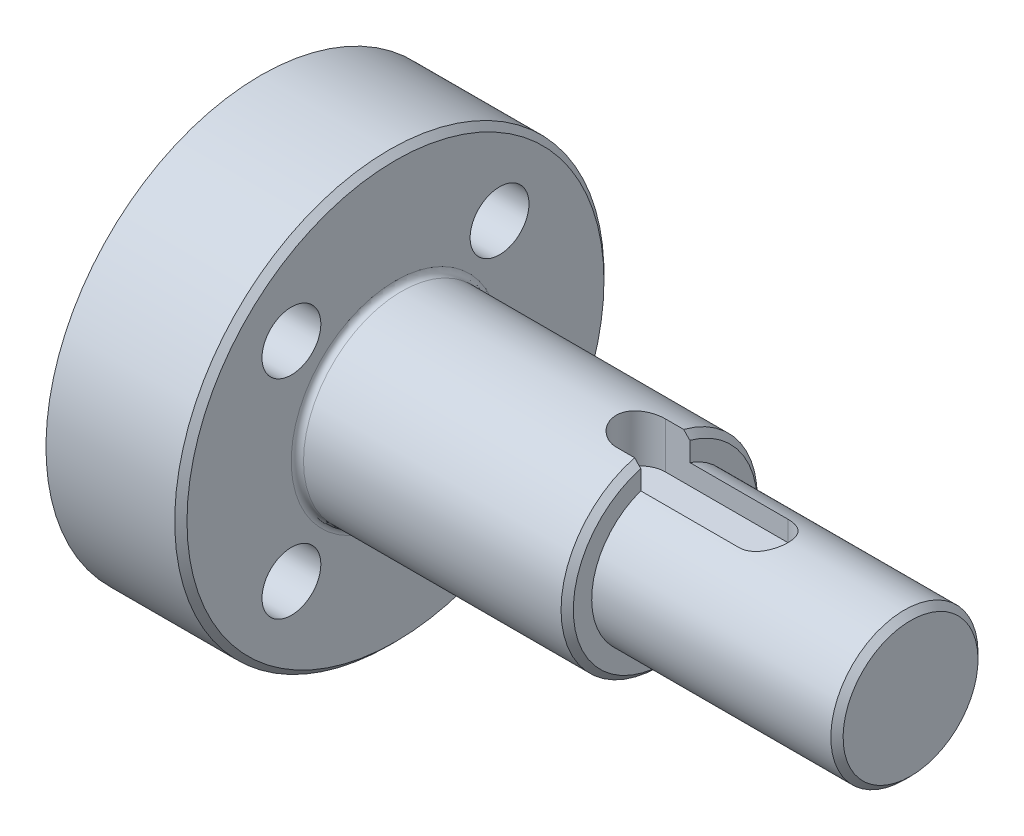
SolidWorks part; units mm, degrees
material "6061-T6 "
ref_plane "Front Plane" through (0, 0, 0) normal (0, 0, 1) x (1, 0, 0)
ref_plane "Top Plane" through (0, 0, 0) normal (0, 1, 0) x (1, 0, 0)
ref_plane "Right Plane" through (0, 0, 0) normal (1, 0, 0) x (0, 0, -1)
sketch "Sketch1" plane through (0, 0, 0) normal (0, 0, 1) x (1, 0, 0)
  line L0 (0, 0) -> (0, 8)
  line L1 (-0.75, 8) -> (-2.5, 8)
  line L2 (-2.5, 8) -> (-2.5, 8.75)
  line L3 (-2.5, 8.75) -> (3, 8.75)
  line L4 (3, 8.75) -> (3, 4)
  line L5 (3, 4) -> (14, 4)
  line L6 (14, 4) -> (14, 3)
  line L7 (14, 3) -> (24, 3)
  line L8 (24, 3) -> (24, 0)
  line L9 (24, 0) -> (0, 0)
  line L11 (6, 4) -> (6, 6) construction
  line L12 (6, 6) -> (9.5, 6) construction
  line L13 (9.5, 6) -> (9.5, 4) construction
  line L14 (14, 4) -> (14, 6.8) construction
  line L15 (14, 6.8) -> (18, 6.8) construction
  line L16 (18, 6.8) -> (18, 3) construction
  line L17 (9.5, 6) -> (11.5, 6) construction
  line L18 (11.5, 6) -> (11.5, 8) construction
  line L19 (0, 0) -> (-3, 0) construction
  line L20 (-3, 0) -> (-3, 8) construction
  line L21 (-3, 8) -> (-2.7343, 8) construction
  line L22 (19, 3) -> (19, 5) construction
  line L23 (19, 5) -> (22, 5) construction
  line L24 (22, 5) -> (22, 3) construction
  line L25 (-0.375, 8.2165) -> (-0.75, 8)
  arc A0 (0, 8) -> (-0.375, 8.2165) centre (-0.25, 8) ccw
  dimension "D22" = 0.5
  dimension "D1" = 8
  dimension "D2" = 2.5
  dimension "D3" = 0.75
  dimension "D4" = 3
  dimension "D5" = 4
  dimension "D7" = 3
  dimension "D8" = 3.5
  dimension "D9" = 6
  dimension "D10" = 3
  dimension "D11" = 2
  dimension "D12" = 4
  dimension "D13" = 6.8
  dimension "D14" = 2.5
  dimension "D15" = 3
  dimension "D16" = 3
  dimension "D17" = 1
  dimension "D18" = 5
  dimension "D19" = 2
  dimension "D21" = 30
revolve "Revolve1" add sketch "Sketch1" angle 360 about L9 region at (9.6178, 2.5742, 0)
hole_wizard "M2 Clearance Hole2" positions "Sketch3" profile "Sketch4" hole size "M2" standard "ANSI Metric" end condition through all
sketch "Sketch3" plane through (3, 0, 0) normal (1, 0, 0) x (0, 0, -1)
  line L0 (-4.2426, 4.2426) -> (4.2426, -4.2426) construction
  line L2 (4.2426, 4.2426) -> (-4.2426, -4.2426) construction
  line L4 (0, 0) -> (0, 6) construction
  circle A0 centre (0, 0) radius 6 construction
  circle A1 centre (-4.2426, 4.2426) radius 1.75 construction
  point P6 (-4.2426, 4.2426)
  point P7 (4.2426, -4.2426)
  point P9 (4.2426, 4.2426)
  point P10 (-4.2426, -4.2426)
  point P25 (-4.2426, 4.2426)
  point P27 (-4.2426, -4.2426)
  point P29 (4.2426, -4.2426)
  point P31 (4.2426, 4.2426)
  dimension "D1" = 12
  dimension "D3" = 3.5
  dimension "D2" = 45
sketch "Sketch4" plane through (3, 4.2426, -4.2426) normal (0, 1, 0) x (0, 0, -1)
  line L0 (0, 0) -> (0, 5.5)
  line L1 (0, 5.5) -> (1.2, 5.5)
  line L2 (1.2, 5.5) -> (1.2, 0)
  line L5 (1.2, 0) -> (0, 0)
  line L11 (0, -6.35) -> (0, 107.95) construction
  dimension "Thru Hole Dia." = 2.4
  dimension "Thru Hole Depth" = 5.5
chamfer "Chamfer2" distance 0.25 angle 45 3 edges at (14, 4, 0) (24, 3, 0) (3, 8.75, 0)
sketch "Sketch5" plane through (0, 0, 0) normal (0, 1, 0) x (1, 0, 0)
  line L0 (14, -3) -> (14, 3) construction
  line L1 (13, 0) -> (18, 0) construction
  line L9 (13, 1) -> (18, 1)
  line L10 (13, -1) -> (18, -1)
  arc A6 (13, 1) -> (13, -1) centre (13, 0) ccw
  arc A7 (18, -1) -> (18, 1) centre (18, 0) ccw
  point P4 (15.5, 0)
  dimension "D3" = 1
  dimension "D1" = 5
  dimension "D2" = 2
extrude "Cut-Extrude1" cut sketch "Sketch5" along normal through all from offset 2
fillet "Fillet1" radius 0.25 1 edges at (3, 4, 0)
